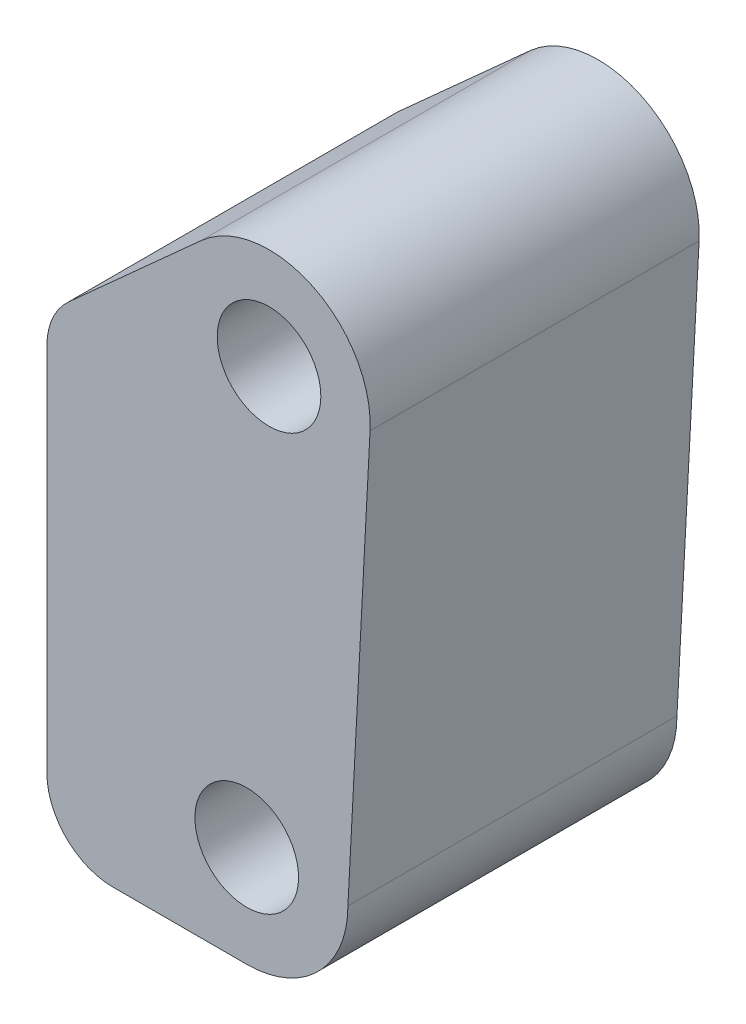
SolidWorks part; units mm, degrees
ref_plane "Front" through (0, 0, 0) normal (0, 0, 1) x (1, 0, 0)
ref_plane "Top" through (0, 0, 0) normal (0, 1, 0) x (1, 0, 0)
ref_plane "Right" through (0, 0, 0) normal (1, 0, 0) x (0, 0, -1)
sketch "Sketch1" plane through (0, 0, 0) normal (0, 0, 1) x (1, 0, 0)
  line L3 (-3.075, 0) -> (-1.575, 0) construction
  line L11 (3.0708, -0.1609) -> (2.3979, -13)
  line L23 (0.8979, -13) -> (2.3979, -13) construction
  line L24 (-0.6771, -16.075) -> (-4.75, -16.075)
  line L25 (-6.75, -14.075) -> (-6.75, -2.8304)
  line L26 (-6.0883, -1.3441) -> (-2.0576, 2.2852)
  circle A0 centre (0, 0) radius 3.075 construction
  circle A3 centre (0, 0) radius 1.575
  circle A12 centre (-0.6771, -13) radius 1.575
  circle A13 centre (-0.6771, -13) radius 3.075 construction
  arc A22 (-2.0576, 2.2852) -> (3.0708, -0.1609) centre (0, 0) cw
  arc A23 (2.3979, -13) -> (-0.6771, -16.075) centre (-0.6771, -13) cw
  arc A24 (-4.75, -16.075) -> (-6.75, -14.075) centre (-4.75, -14.075) cw
  arc A25 (-6.75, -2.8304) -> (-6.0883, -1.3441) centre (-4.75, -2.8304) cw
  point P0 (-6.0748, -1.2664)
  point P21 (0, 0)
  dimension "D1" = 3.15
  dimension "D4" = 2
  dimension "D2" = 1.5
  dimension "D3" = 6.75
  dimension "D5" = 42
  dimension "D6" = 87
  dimension "D7" = 13
extrude "Boss-Extrude1" add sketch "Sketch1" along normal mid plane 10 contours A3 region at (-1.989, -7.0323, 0)
equation "\"D1@Sketch1\"=\"Hardware Clearance Hole Diameter@Box Assy.Assembly\""
